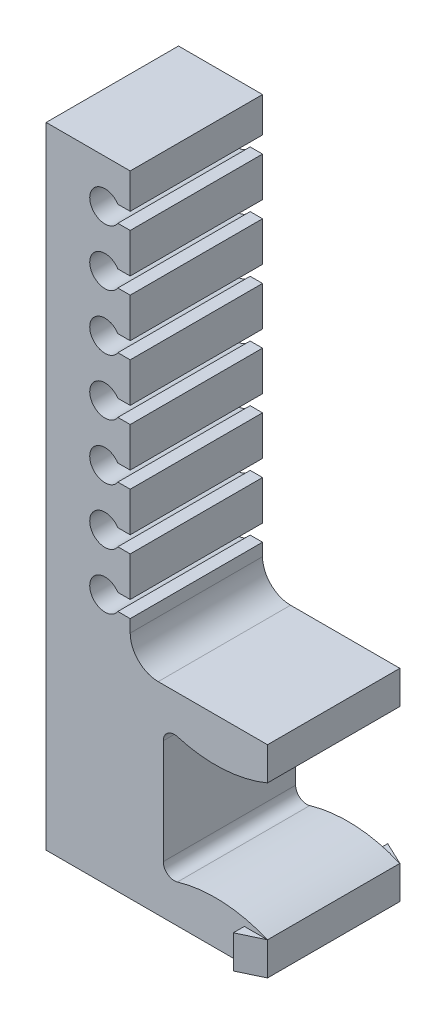
SolidWorks part; units mm, degrees
ref_plane "Front Plane" through (0, 0, 0) normal (0, 0, 1) x (1, 0, 0)
ref_plane "Top Plane" through (0, 0, 0) normal (0, 1, 0) x (1, 0, 0)
ref_plane "Right Plane" through (0, 0, 0) normal (1, 0, 0) x (0, 0, -1)
sketch "Sketch1" plane through (0, 0, 0) normal (0, 0, 1) x (1, 0, 0)
  line L2 (-159.7982, 9.1594) -> (-172.2482, 9.1594)
  line L3 (-172.2482, 9.1594) -> (-172.2482, -9.1594)
  line L7 (-169.2482, -22.8519) -> (-169.2482, 6.1594) construction
  line L13 (-142.8048, 5.1594) -> (-142.8048, -5.1594) construction
  line L23 (-159.7982, 6.1594) -> (-159.7982, 9.1594)
  line L28 (-164.5232, 5.2094) -> (-144.5007, 5.2094) construction
  line L30 (-169.2482, 6.1594) -> (-169.2482, 5.1594)
  line L34 (-169.2482, 5.1594) -> (-169.2482, -5.1594)
  line L35 (-172.2482, 0) -> (-169.2482, 0) construction
  line L36 (-169.2482, -6.1594) -> (-169.2482, -5.1594)
  line L37 (-159.7982, -6.1594) -> (-159.7982, -9.1594)
  line L38 (-159.7982, -9.1594) -> (-172.2482, -9.1594)
  arc A5 (-169.2482, 6.1594) -> (-159.7982, 6.1594) centre (-164.5232, 17.4347) ccw
  arc A6 (-169.2482, -6.1594) -> (-159.7982, -6.1594) centre (-164.5232, -17.4347) cw
  point P30 (-142.8048, 0)
  dimension "D6" = 12.2253
  dimension "D4" = 3
  dimension "D3" = 3
  dimension "D2" = 1
  dimension "D1" = 18.3188
  dimension "D5" = 12.45
extrude "MainBody" add sketch "Sketch1" along normal mid plane 12
sketch "Sketch3" plane through (0, -9.1594, 0) normal (0, -1, 0) x (1, 0, 0)
  line L0 (-159.7982, -6) -> (-161.8982, -7)
  line L1 (-161.8982, -7) -> (-161.8982, -6)
  line L2 (-172.2482, -6) -> (-159.7982, -6) construction
  line L3 (-161.8982, -6) -> (-159.7982, -6)
  line L5 (8.8033, 0) -> (-8.8033, 0) construction
  line L6 (-161.8982, 6) -> (-159.7982, 6)
  line L7 (-161.8982, 7) -> (-161.8982, 6)
  line L8 (-159.7982, 6) -> (-161.8982, 7)
  dimension "D1" = 2.1
  dimension "D2" = 1
extrude "Hook" add sketch "Sketch3" against normal up to vertex (3 mm away) up to point (-159.7982, -6.1594, -6)
fillet "Fillet2" radius 1 2 edges at (-169.2482, 6.1594, 0) (-169.2482, -6.1594, 0)
sketch "Sketch5" [suppressed] plane through (-172.2482, 0, 0) normal (-1, 0, 0) x (0, 0, 1)
  line L1 (-6, 9.1594) -> (6, 9.1594)
  line L2 (-6, 9.1594) -> (-6, -9.1594)
  line L3 (-6, -9.1594) -> (6, -9.1594)
  line L4 (6, 9.1594) -> (6, -9.1594)
extrude "Boss-Extrude1" [suppressed] add sketch "Sketch5" along normal blind 15
sketch "Sketch6" [suppressed] plane through (0, 9.1594, 0) normal (0, 1, 0) x (1, 0, 0)
  line L0 (-187.2482, -6) -> (-187.2482, 6) construction
  circle A0 centre (-182.2482, 0) radius 3.302
  dimension "D1" = 6.604
  dimension "D2" = 5
extrude "Cut-Extrude2" [suppressed] cut sketch "Sketch6" against normal through all
sketch "Sketch7" [suppressed] plane through (-172.2482, 0, 0) normal (-1, 0, 0) x (0, 0, 1)
  circle A0 centre (0, 0) radius 38.1
  dimension "D1" = 76.2
extrude "Boss-Extrude2" [suppressed] add sketch "Sketch7" along normal blind 5
fillet "Fillet3" [suppressed] radius 1
sketch "Sketch8" [suppressed] plane through (0, 0, 6) normal (0, 0, 1) x (1, 0, 0)
  line L6 (-172.2482, -0.635) -> (-173.4343, -0.635)
  line L8 (-172.2482, 0.635) -> (-173.4343, 0.635)
  line L10 (-172.2482, 0.635) -> (-173.4343, 0.635)
  line L11 (-172.2482, 0.635) -> (-172.2482, -0.635)
  line L12 (-159.7982, -9.1594) -> (-159.7982, -6.1594)
  line L13 (-159.7982, -9.1594) -> (-159.7982, -6.1594)
  line L14 (-169.2482, -6.1594) -> (-169.2482, 6.1594)
  line L15 (-159.7982, 6.1594) -> (-159.7982, 9.1594)
  line L16 (-159.7982, 9.1594) -> (-172.2482, 9.1594)
  line L17 (-172.2482, 9.1594) -> (-172.2482, -9.1594)
  line L18 (-172.2482, -9.1594) -> (-159.7982, -9.1594)
  line L21 (-169.2482, -6.1594) -> (-169.2482, 6.1594)
  line L22 (-159.7982, 6.1594) -> (-159.7982, 9.1594)
  line L23 (-159.7982, 9.1594) -> (-172.2482, 9.1594)
  line L24 (-172.2482, 9.1594) -> (-172.2482, -9.1594)
  line L25 (-172.2482, -9.1594) -> (-159.7982, -9.1594)
  line L26 (-172.2482, -0.635) -> (-173.4343, -0.635)
  arc A0 (-173.4343, 0.635) -> (-173.4343, -0.635) centre (-174.5342, 0) ccw
  arc A4 (-159.7982, -6.1594) -> (-169.2482, -6.1594) centre (-164.5232, -17.4347) ccw
  arc A7 (-169.2482, 6.1594) -> (-159.7982, 6.1594) centre (-164.5232, 17.4347) ccw
  arc A8 (-159.7982, -6.1594) -> (-169.2482, -6.1594) centre (-164.5232, -17.4347) ccw
  arc A11 (-169.2482, 6.1594) -> (-159.7982, 6.1594) centre (-164.5232, 17.4347) ccw
  point P6 (-172.2482, 0)
  line M14 (-172.2482, 9.1594) -> (-172.2482, -9.1594)
  dimension "D2" = 1.27
  dimension "D1" = 0
  dimension "D3" = 2.286
extrude "Slot" [suppressed] add sketch "Sketch8" against normal up to surface (12 mm away) contours L8 A0 L6 M14 up to face at (-165.6835, -0.5599, -6)
sketch "Sketch10" [suppressed] plane through (0, 0, -6) normal (0, 0, -1) x (-1, 0, 0)
  line L0 (166.0232, -9.1594) -> (172.2482, -9.1594)
  line L3 (172.2482, -9.1594) -> (166.0232, -9.1594)
  line L5 (172.2482, -9.1594) -> (187.9767, -44.4861)
  line L6 (195.4932, -61.3685) -> (192.3182, -61.3685)
  line L7 (159.7982, -6.1594) -> (159.7982, -9.1594)
  line L8 (159.7982, -6.1594) -> (159.7982, -9.1594)
  line L9 (159.7982, -9.1594) -> (172.2482, -9.1594)
  line L10 (172.2482, -9.1594) -> (172.2482, 9.1594)
  line L11 (172.2482, 9.1594) -> (159.7982, 9.1594)
  line L12 (159.7982, 9.1594) -> (159.7982, 6.1594)
  line L13 (169.2482, 6.1594) -> (169.2482, -6.1594)
  line L16 (159.7982, -9.1594) -> (172.2482, -9.1594)
  line L17 (172.2482, -9.1594) -> (172.2482, 9.1594)
  line L18 (172.2482, 9.1594) -> (159.7982, 9.1594)
  line L19 (159.7982, 9.1594) -> (159.7982, 6.1594)
  line L20 (169.2482, 6.1594) -> (169.2482, -6.1594)
  line L21 (195.4932, -61.3685) -> (201.8432, -61.3685)
  line L22 (201.8432, -61.3685) -> (201.8432, -59.781)
  line L24 (192.666, -55.0185) -> (200.9772, -55.0185)
  line L25 (169.0732, -9.1594) -> (192.3182, -61.3685)
  line L28 (201.8432, -59.781) -> (194.7864, -59.781)
  line L31 (193.3728, -56.606) -> (200.9772, -56.606)
  line L42 (200.9772, -55.0185) -> (200.9772, -56.606)
  line L43 (187.9767, -44.4861) -> (195.4932, -61.3685)
  arc A4 (169.2482, -6.1594) -> (159.7982, -6.1594) centre (164.5232, -17.4347) ccw
  arc A5 (159.7982, 6.1594) -> (169.2482, 6.1594) centre (164.5232, 17.4347) ccw
  arc A8 (169.2482, -6.1594) -> (159.7982, -6.1594) centre (164.5232, -17.4347) ccw
  arc A9 (159.7982, 6.1594) -> (169.2482, 6.1594) centre (164.5232, 17.4347) ccw
  dimension "D5" = 6.35
  dimension "D7" = 3.175
  dimension "D8" = 3.175
  dimension "D2" = 57.15
  dimension "D10" = 1.5875
  dimension "D13" = 114
  dimension "D14" = 114
  dimension "D3" = 1.5875
  dimension "D4" = 3.175
extrude "Boss-Extrude3" [suppressed] add sketch "Sketch10" against normal up to surface (12 mm away) up to face at (-165.6835, -0.5599, 6)
sketch "Sketch11" [suppressed] plane through (0, 0, -6) normal (0, 0, -1) x (-1, 0, 0)
  line L0 (159.7982, -9.1594) -> (159.7982, 9.1594)
  line L11 (169.2482, 6.1594) -> (169.2482, -6.1594)
  line L12 (159.7982, -6.1594) -> (159.7982, -9.1594)
  line L13 (159.7982, -9.1594) -> (169.0732, -9.1594)
  line L14 (169.0732, -9.1594) -> (192.3182, -61.3685)
  line L15 (192.3182, -61.3685) -> (201.8432, -61.3685)
  line L16 (201.8432, -61.3685) -> (201.8432, -59.781)
  line L17 (201.8432, -59.781) -> (194.7864, -59.781)
  line L18 (194.7864, -59.781) -> (193.3728, -56.606)
  line L19 (172.2482, -9.1594) -> (172.2482, 9.1594)
  line L20 (172.2482, 9.1594) -> (159.7982, 9.1594)
  line L21 (159.7982, 9.1594) -> (159.7982, 6.1594)
  line L22 (169.2482, 6.1594) -> (169.2482, -6.1594)
  line L23 (159.7982, -6.1594) -> (159.7982, -9.1594)
  line L24 (159.7982, -9.1594) -> (169.0732, -9.1594)
  line L25 (169.0732, -9.1594) -> (192.3182, -61.3685)
  line L26 (192.3182, -61.3685) -> (201.8432, -61.3685)
  line L27 (201.8432, -61.3685) -> (201.8432, -59.781)
  line L28 (201.8432, -59.781) -> (194.7864, -59.781)
  line L29 (194.7864, -59.781) -> (193.3728, -56.606)
  line L30 (172.2482, -9.1594) -> (172.2482, 9.1594)
  line L31 (172.2482, 9.1594) -> (159.7982, 9.1594)
  line L32 (159.7982, 9.1594) -> (159.7982, 6.1594)
  line L37 (193.3728, -56.606) -> (200.9772, -56.606)
  line L38 (193.3728, -56.606) -> (200.9772, -56.606)
  line L39 (200.9772, -56.606) -> (200.9772, -55.0185)
  line L40 (200.9772, -56.606) -> (200.9772, -55.0185)
  line L41 (192.666, -55.0185) -> (172.2482, -9.1594)
  line L42 (192.666, -55.0185) -> (172.2482, -9.1594)
  line L44 (200.9772, -55.0185) -> (192.666, -55.0185)
  line L45 (200.9772, -55.0185) -> (192.666, -55.0185)
  arc A2 (159.7982, 6.1594) -> (169.2482, 6.1594) centre (164.5232, 17.4347) ccw
  arc A3 (169.2482, -6.1594) -> (159.7982, -6.1594) centre (164.5232, -17.4347) ccw
  arc A4 (159.7982, 6.1594) -> (169.2482, 6.1594) centre (164.5232, 17.4347) ccw
  arc A5 (169.2482, -6.1594) -> (159.7982, -6.1594) centre (164.5232, -17.4347) ccw
  arc M14 (159.7982, 6.1594) -> (169.2482, 6.1594) centre (164.5232, 17.4347) ccw
  line M15 (169.2482, 6.1594) -> (169.2482, -6.1594)
  arc M16 (169.2482, -6.1594) -> (159.7982, -6.1594) centre (164.5232, -17.4347) ccw
  dimension "D1" = 0
extrude "Boss-Extrude4" [suppressed] add sketch "Sketch11" against normal up to surface (12 mm away) contours L0 M16 M15 M14 up to face at (-165.6835, -0.5599, 6)
sketch "Sketch12" [suppressed] plane through (0, 0, -6) normal (0, 0, -1) x (-1, 0, 0)
  line L0 (159.7982, -9.1594) -> (159.7982, -5.9844)
  line L1 (159.7982, -5.9844) -> (162.0842, -5.9844)
  line L3 (162.0842, -5.2351) -> (159.7982, -5.2351)
  line L4 (162.0842, -5.2351) -> (162.0842, -6.7337)
  line L5 (162.0842, -6.7337) -> (159.7982, -6.7337)
  line L6 (159.7982, -5.2351) -> (159.7982, -6.7337)
  line L7 (162.0842, -5.2351) -> (159.7982, -6.7337) construction
  line L8 (162.0842, -6.7337) -> (159.7982, -5.2351) construction
  line L9 (172.2482, 9.1594) -> (159.7982, 9.1594)
  line L10 (159.7982, 9.1594) -> (159.7982, -9.1594)
  line L11 (159.7982, -9.1594) -> (169.0732, -9.1594)
  line L12 (169.0732, -9.1594) -> (192.3182, -61.3685)
  line L13 (192.3182, -61.3685) -> (201.8432, -61.3685)
  line L14 (201.8432, -61.3685) -> (201.8432, -59.781)
  line L15 (201.8432, -59.781) -> (194.7864, -59.781)
  line L16 (194.7864, -59.781) -> (193.3728, -56.606)
  line L17 (172.2482, -9.1594) -> (172.2482, 9.1594)
  line L18 (172.2482, 9.1594) -> (159.7982, 9.1594)
  line L19 (159.7982, 9.1594) -> (159.7982, -9.1594)
  line L20 (159.7982, -9.1594) -> (169.0732, -9.1594)
  line L21 (169.0732, -9.1594) -> (192.3182, -61.3685)
  line L22 (192.3182, -61.3685) -> (201.8432, -61.3685)
  line L23 (201.8432, -61.3685) -> (201.8432, -59.781)
  line L24 (201.8432, -59.781) -> (194.7864, -59.781)
  line L25 (194.7864, -59.781) -> (193.3728, -56.606)
  line L26 (172.2482, -9.1594) -> (172.2482, 9.1594)
  line L38 (193.3728, -56.606) -> (200.9772, -56.606)
  line L39 (193.3728, -56.606) -> (200.9772, -56.606)
  line L40 (200.9772, -56.606) -> (200.9772, -55.0185)
  line L42 (192.666, -55.0185) -> (172.2482, -9.1594)
  line L43 (192.666, -55.0185) -> (172.2482, -9.1594)
  line L45 (200.9772, -56.606) -> (200.9772, -55.0185)
  line L46 (200.9772, -55.0185) -> (192.666, -55.0185)
  line L47 (200.9772, -55.0185) -> (192.666, -55.0185)
  circle A0 centre (162.0842, -5.9844) radius 1.3843
  point P8 (160.9412, -5.9844)
  line M13 (159.7982, 9.1594) -> (159.7982, -9.1594)
  dimension "D4" = 2.7686
  dimension "D2" = 3.175
  dimension "D3" = 2.286
  dimension "D5" = 1.4986
extrude "Cut-Extrude3" [suppressed] cut sketch "Sketch12" against normal up to surface (12 mm away) contours L5 A0 L3 L4 | L1 A0 L5 L4 | A0 L1 L5 M13 | L3 A0 L1 L4 | A0 L3 L1 M13 up to face at (-165.6835, -0.5599, 6)
pattern_linear "LPattern1" [suppressed] count 4 spacing 4.28 of bodies 117
sketch "Sketch15" plane through (0, 0, 6) normal (0, 0, 1) x (1, 0, 0)
  line L1 (-172.2482, -9.1594) -> (-179.8682, -9.1594)
  line L2 (-172.2482, -9.1594) -> (-172.2482, 47.9906)
  line L3 (-172.2482, 47.9906) -> (-179.8682, 47.9906)
  line L4 (-179.8682, -9.1594) -> (-179.8682, 47.9906)
  dimension "D1" = 7.62
  dimension "D2" = 57.15
extrude "Boss-Extrude6" add sketch "Sketch15" against normal up to surface (12 mm away) up to face at (-165.6835, -0.5599, -6)
sketch "Sketch16" plane through (0, 0, 6) normal (0, 0, 1) x (1, 0, 0)
  line L0 (-172.2482, 9.1594) -> (-172.2482, 47.9906) construction
  line L1 (-172.2482, 44.8156) -> (-174.5342, 44.8156)
  line L2 (-172.2482, 44.8156) -> (-172.2482, 43.317)
  line L3 (-172.2482, 43.317) -> (-174.5342, 43.317)
  line L4 (-174.5342, 44.8156) -> (-174.5342, 43.317)
  line L5 (-172.2482, 47.9906) -> (-179.8682, 47.9906) construction
  circle A0 centre (-174.5342, 44.0663) radius 1.3843
  line M12 (-172.2482, 9.1594) -> (-172.2482, 47.9906)
  dimension "D4" = 2.7686
  dimension "D1" = 3.175
  dimension "D2" = 1.4986
  dimension "D3" = 2.286
extrude "Cut-Extrude6" cut sketch "Sketch16" against normal up to surface (12 mm away) contours A0 L3 L1 M12 | L3 A0 L1 L4 | L1 A0 L3 L4 region at (-172.7367, 44.0663, 6) region at (-173.8759, 44.0663, 6) region at (-174.8539, 44.0663, 6) up to face at (-167.8658, 6.9094, -6)
pattern_linear "LPattern3" count 7 spacing 5.08 along (0, -1, 0) of "Cut-Extrude6"
fillet "Fillet5" radius 2.54 1 edges at (-172.2482, 9.1594, 0)
equation "\"HookThickness\"= 3mm"
equation "\"D3@Sketch1\"=\"HookThickness\""
equation "\"D4@Sketch1\"=\"HookThickness\""
equation "\"CylinderDiameter\"=3"
equation "\"D1@Sketch7\"=\"CylinderDiameter\""
equation "\"Mount Tolerance\"= .005in"
equation "\"Mount Thickness\"= .0625in"
equation "\"Mount Angle\"= 114"
equation "\"D14@Sketch10\"=\"Mount Angle\""
equation "\"D13@Sketch10\"= \"Mount Angle\""
equation "\"Joint Radius\"= .05in"
equation "\"Joint Thickness\"= .05in"
equation "\"Joint Tolerance\"= .009in"
equation "\"D4@Sketch12\"= (\"Joint Radius\" * 2) + \"Joint Tolerance\""
equation "\"D5@Sketch12\"= \"Joint Thickness\" + \"Joint Tolerance\""
